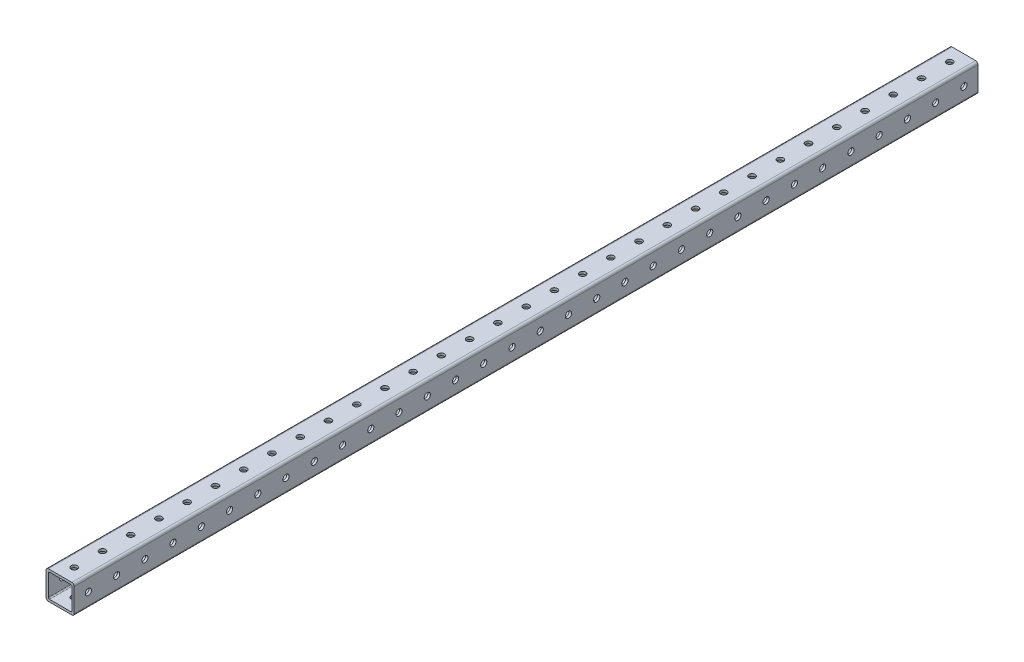
SolidWorks part; units mm, degrees
material "6063-T4"
ref_plane "Front Plane" through (0, 0, 0) normal (0, 0, 1) x (1, 0, 0)
ref_plane "Top Plane" through (0, 0, 0) normal (0, 1, 0) x (1, 0, 0)
ref_plane "Right Plane" through (0, 0, 0) normal (1, 0, 0) x (0, 0, -1)
sketch "Sketch1" plane through (0, 0, 0) normal (0, 0, 1) x (1, 0, 0)
  line L0 (-19.05, -19.05) -> (19.05, 19.05) construction
  line L1 (-15.875, 19.05) -> (15.875, 19.05)
  line L2 (-19.05, 15.875) -> (-19.05, -15.875)
  line L3 (-15.875, -19.05) -> (15.875, -19.05)
  line L4 (19.05, 15.875) -> (19.05, -15.875)
  arc A0 (15.875, 19.05) -> (19.05, 15.875) centre (15.875, 15.875) cw
  arc A1 (15.875, -19.05) -> (19.05, -15.875) centre (15.875, -15.875) ccw
  arc A2 (-19.05, -15.875) -> (-15.875, -19.05) centre (-15.875, -15.875) ccw
  arc A3 (-15.875, 19.05) -> (-19.05, 15.875) centre (-15.875, 15.875) ccw
  dimension "D1" = 3.175
  dimension "D2" = 38.1
extrude "Extrude-Thin1" add sketch "Sketch1" along normal mid plane 1219.2 thin thin type one direction reverse wall 3.175
fillet "Fillet1" radius 1.6002 4 edges at (15.875, -15.875, 0) (15.875, 15.875, 0) (-15.875, 15.875, 0) (-15.875, -15.875, 0)
sketch "Sketch2" plane through (0, 0, 0) normal (0, 1, 0) x (1, 0, 0)
  line L0 (14.2748, -609.6) -> (-14.2748, -609.6) construction
  line L1 (0, -590.55) -> (0, -552.45) construction
  circle A0 centre (0, -590.55) radius 4.1656
  point P2 (0, -609.6)
  dimension "Bolt Hole" = 8.3312
  dimension "1/2 of Center to Center" = 19.05
  dimension "Center to Center" = 38.1
extrude "Cut-Extrude1" cut sketch "Sketch2" against normal through all and the other way through all
ref_axis "Axis1" through (0, 0, 590.55) along (0, 0, -1)
pattern_linear "LPattern1" count 32 spacing 38.1 along (0, 0, -1) of "Cut-Extrude1"
pattern_circular "CirPattern1" count 2 over 90 about axis through (0, 0, 590.55) along (0, 0, -1) of "LPattern1"
equation "\"1/2 of Center to Center@Sketch2\" = \"Center to Center@Sketch2\"/2"
equation "\"D1@LPattern1\" = \"Length@Extrude-Thin1\"/\"Center to Center@Sketch2\""
equation "\"D3@LPattern1\" = \"Center to Center@Sketch2\""
